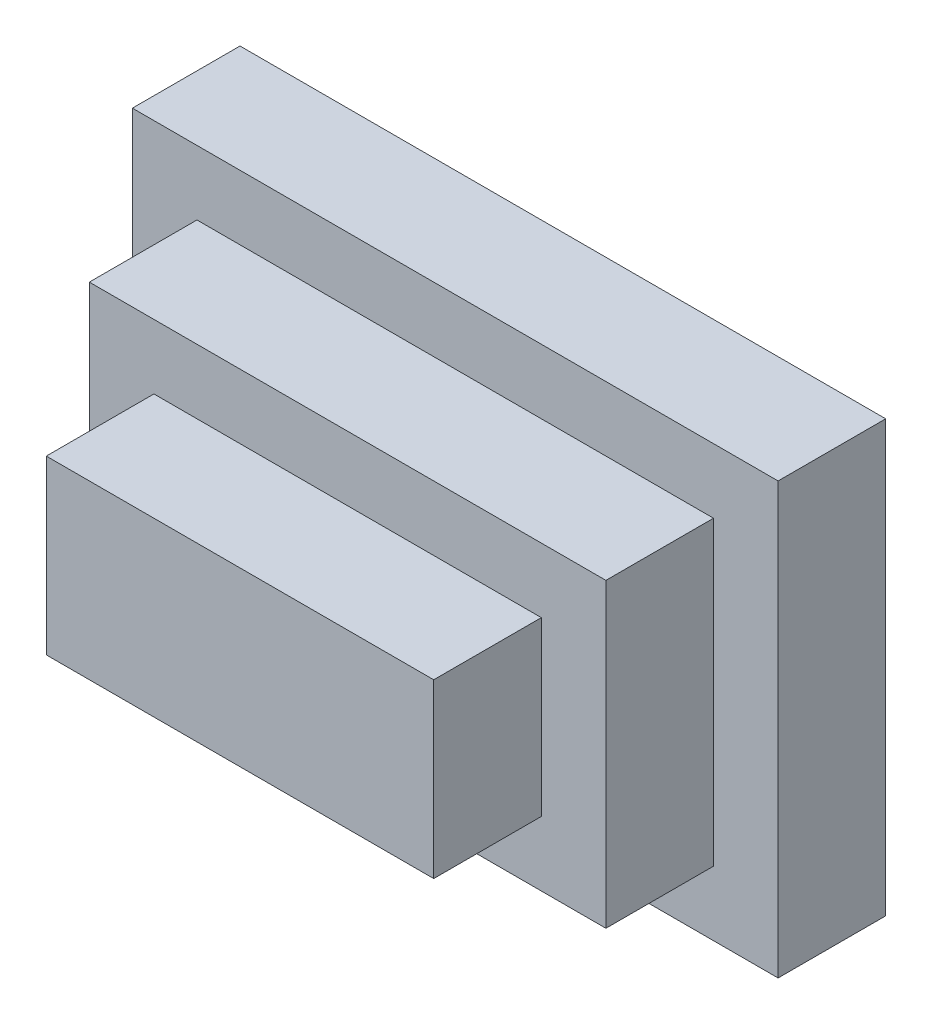
SolidWorks part; units mm, degrees
ref_plane "Front Plane" through (0, 0, 0) normal (0, 0, 1) x (1, 0, 0)
ref_plane "Top Plane" through (0, 0, 0) normal (0, 1, 0) x (1, 0, 0)
ref_plane "Right Plane" through (0, 0, 0) normal (1, 0, 0) x (0, 0, -1)
sketch "Sketch2" plane through (0, 0, 0) normal (0, 0, 1) x (1, 0, 0)
  line L1 (-150, 100) -> (150, 100)
  line L2 (-150, 100) -> (-150, -100)
  line L3 (-150, -100) -> (150, -100)
  line L4 (150, 100) -> (150, -100)
  line L5 (-150, 100) -> (150, -100) construction
  line L6 (-150, -100) -> (150, 100) construction
  point P0 (0, 0)
  dimension "D1" = 300
  dimension "D2" = 200
extrude "Boss-Extrude1" add sketch "Sketch2" along normal blind 50
sketch "Sketch3" plane through (0, 0, 50) normal (0, 0, 1) x (1, 0, 0)
  line L14 (-120, -70) -> (120, -70)
  line L15 (120, -70) -> (120, 70)
  line L16 (-120, 70) -> (-120, -70)
  line L17 (120, 70) -> (-120, 70)
  line L18 (-120, -70) -> (120, -70)
  line L19 (120, -70) -> (120, 70)
  line L20 (-120, 70) -> (-120, -70)
  line L21 (120, 70) -> (-120, 70)
  dimension "D1" = 30
extrude "Boss-Extrude2" add sketch "Sketch3" along normal blind 50
sketch "Sketch4" plane through (0, 0, 100) normal (0, 0, 1) x (1, 0, 0)
  line L14 (-90, -40) -> (90, -40)
  line L15 (90, -40) -> (90, 40)
  line L16 (90, 40) -> (-90, 40)
  line L17 (-90, 40) -> (-90, -40)
  line L18 (-90, -40) -> (90, -40)
  line L19 (90, -40) -> (90, 40)
  line L20 (90, 40) -> (-90, 40)
  line L21 (-90, 40) -> (-90, -40)
  dimension "D1" = 30
extrude "Boss-Extrude3" add sketch "Sketch4" along normal blind 50
extrude "Cut-Extrude1" cut sketch "Sketch3<2>" against normal blind 50
sketch "Sketch3<2>" plane through (0, 0, 50) normal (0, 0, 1) x (1, 0, 0) same geometry as "Sketch3"
extrude "Cut-Extrude2" cut sketch "Sketch4<2>" against normal blind 50
sketch "Sketch4<2>" plane through (0, 0, 100) normal (0, 0, 1) x (1, 0, 0) same geometry as "Sketch4"
